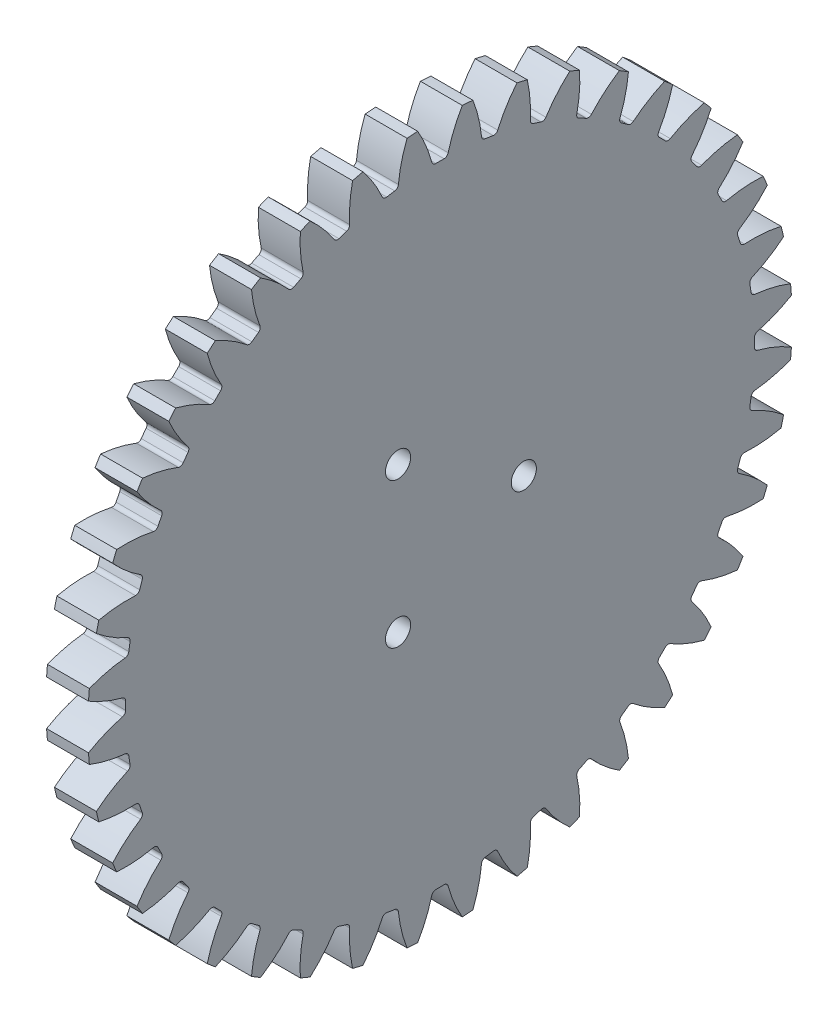
SolidWorks part; units mm, degrees
material "Delrin 2700 NC010, Low Viscosity Acetal Copolymer (SS)"
ref_plane "Plane1" through (0, 0, 0) normal (0, 0, 1) x (1, 0, 0)
ref_plane "Plane2" through (0, 0, 0) normal (0, 1, 0) x (1, 0, 0)
ref_plane "Plane3" through (0, 0, 0) normal (1, 0, 0) x (0, 0, -1)
sketch "HoldingSke" plane through (0, 0, 0) normal (0, 1, 0) x (1, 0, 0)
  line L0 (0, 0) -> (0.383, -0.3214)
  line L1 (-15, 0) -> (100, 0) construction
  line L2 (0, 0) -> (-2.1039, 2.3779)
  line L3 (0, 0) -> (-11.863, 4.5341)
  line L4 (0, 0) -> (6.6156, 5.5511)
  line L5 (0, 0) -> (-46.8476, -17.4728)
  line L6 (0, 0) -> (-4.1448, -2.7965)
  line L7 (-2.1039, 2.3779) -> (8.6586, 51.2059)
  line L8 (-76.2, 54.61) -> (-76.1, 54.61)
  line L9 (-71.009, 38.7566) -> (-53.1078, 45.2721)
  line L10 (-76.2, 71.12) -> (104.1128, 71.12)
  line L11 (0, 0) -> (-5, 0)
  line L12 (-76.2, 101.6) -> (-76.133, 101.6)
  line L13 (24.9733, 27.94) -> (52.9518, 28.4284)
  line L14 (24.9733, 27.94) -> (24.9743, 27.94)
  line L15 (24.9733, 27.94) -> (100.4006, 29.5858)
  line L16 (-63.627, -2) -> (-12.827, -2)
  circle A0 centre (0, 0) radius 0.4
  circle A1 centre (0, 0) radius 37.499
  circle A2 centre (0, 0) radius 37.5
  circle A3 centre (0, 0) radius 0.4
  dimension "MHD" = 74.998
  dimension "Hub_dia" = 75
  dimension "Bore" = 0.8
  dimension "MBD" = 0.8
  dimension "Num_teeth" = 40
  dimension "Pitch" = 0.5
  dimension "Overall_len" = 50
  dimension "Show_teeth" = 40
  dimension "Thickness" = 5
  dimension "OAL" = 50.0001
  dimension "T_dim" = 0.1
  dimension "Ap" = 20
  dimension "H" = 19.05
  dimension "Pitch_radius" = 180.3128
  dimension "Width" = 5
  dimension "Backlash" = 0.067
  dimension "Addendum_fac" = 1
  dimension "Dedendum_fac" = 1.25
  dimension "Clearance_fac" = 0.25
  dimension "Dedendum_add" = 0.001
  dimension "Module" = 2
sketch "BasProSke" plane through (0, 0, 0) normal (0, 1, 0) x (1, 0, 0)
  line L0 (-10, 0) -> (60, 0) construction
  line L1 (0, 0) -> (0, 42)
  line L2 (0, 0) -> (5, 0)
  line L3 (5, 0) -> (5, 42)
  line L4 (5, 42) -> (0, 42)
  dimension "Thickness" = 5
  dimension "Diameter" = 84
revolve "Base-Revolve" add sketch "BasProSke" angle 360 about L0
sketch "TooCutSke" plane through (0, 0, 0) normal (1, 0, 0) x (0, 0, -1)
  line L1 (0, 0) -> (0, 107) construction
  line L2 (0, 0) -> (-1.6876, 39.9644) construction
  line L3 (0, 0) -> (-6.2726, 79.7007) construction
  line L4 (-1.6876, 39.9644) -> (-3.1363, 39.8504) construction
  arc A0 (0.8828, 37.4886) -> (-0.8828, 37.4886) centre (0, 0) ccw
  arc A1 (2.6784, 41.94) -> (-2.6784, 41.94) centre (0, 0) ccw
  circle A2 centre (0, 0) radius 40 construction
  circle A3 centre (0, 0) radius 37.5877 construction
  arc A4 (-0.8828, 37.4886) -> (-2.6784, 41.94) centre (-16.451, 33.7965) ccw
  arc A5 (2.6784, 41.94) -> (0.8828, 37.4886) centre (16.451, 33.7965) ccw
  dimension "Root_dia" = 74.998
  dimension "Overcut_dia" = 84.0508
  dimension "Pitch_dia" = 80
  dimension "Base_dia" = 75.1754
  dimension "Flank_rad" = 16
  dimension "Half_ang" = 4.5
  dimension "Half_CT" = 1.4531
extrude "ToothCut" cut sketch "TooCutSke" along normal through all
fillet "Breaks" [suppressed] radius 0.04 tangent propagation no
fillet "RootFillets" radius 0.501 2 edges at (2.5, 37.4886, -0.8828) (2.5, 37.4886, 0.8828)
pattern_circular "TeethCuts" count 40 every 9 about axis through (-10, 0, 0) along (1, 0, 0) of "ToothCut", "RootFillets", "Breaks"
sketch "HubNeaOneSke" plane through (0, 0, 0) normal (-1, 0, 0) x (0, 0, 1)
  circle A0 centre (0, 0) radius 37.499
  dimension "Diameter" = 74.998
extrude "HubNearOne" [suppressed] add sketch "HubNeaOneSke" along normal blind 45.0001
sketch "HubNeaBotSke" plane through (0, 0, 0) normal (-1, 0, 0) x (0, 0, 1)
  circle A0 centre (0, 0) radius 37.499
  dimension "Diameter" = 74.998
extrude "HubNearBoth" [suppressed] add sketch "HubNeaBotSke" along normal blind 22.5
ref_plane "FarPln" through (5, 0, 0) normal (1, 0, 0) x (0, 0, -1)
sketch "HubFarSke" plane through (5, 0, 0) normal (1, 0, 0) x (0, 0, -1)
  circle A0 centre (0, 0) radius 37.499
  dimension "Diameter" = 74.998
extrude "HubFar" [suppressed] add sketch "HubFarSke" along normal blind 22.5
sketch "BorSke" plane through (0, 0, 0) normal (1, 0, 0) x (0, 0, -1)
  circle A0 centre (0, 0) radius 0.4
  dimension "Diameter" = 0.8
extrude "Bore" [suppressed] cut sketch "BorSke" along normal mid plane 100.0001
sketch "KeySke" plane through (0, 0, 0) normal (1, 0, 0) x (0, 0, -1)
  line L0 (-0.05, 0) -> (-0.05, 0.5)
  line L1 (-0.05, 0.5) -> (0.05, 0.5)
  line L2 (0.05, 0.5) -> (0.05, 0)
  line L3 (0, 0) -> (0, 34) construction
  line L4 (-0.05, 0) -> (0.05, 0)
  dimension "Offset" = 0.5
  dimension "Width" = 0.1
extrude "Keyway" [suppressed] cut sketch "KeySke" along normal mid plane 100.0001
pattern_circular "Keyway2" [suppressed] count 2 every 90 about axis through (-10, 0, 0) along (1, 0, 0) reverse direction yes
sketch "Sketch1" plane through (5, 0, 0) normal (1, 0, 0) x (0, 0, -1)
  line L0 (0, 0) -> (10, 0)
  line L1 (0, 0) -> (-5, 8.6603)
  line L2 (0, 0) -> (-5, -8.6603)
  circle A0 centre (-5, -8.6603) radius 1.5
  circle A1 centre (-5, 8.6603) radius 1.5
  circle A2 centre (10, 0) radius 1.5
  dimension "D6" = 3
  dimension "D7" = 3
  dimension "D8" = 3
  dimension "D1" = 10
  dimension "D2" = 10
  dimension "D3" = 10
  dimension "D4" = 120
  dimension "D5" = 120
extrude "Cut-Extrude1" cut sketch "Sketch1" against normal through all contours A2 | A0 | A1
equation "' \"Module@HoldingSke\" = 6.35"
equation "' \"Num_teeth@HoldingSke\" = 12"
equation "' \"Ap@HoldingSke\" =  20"
equation "' \"Ap@HoldingSke\" = 20"
equation "' \"Width@HoldingSke\" = 0.5 * 25.4"
equation "' \"Hub_dia@HoldingSke\"= 1 * 25.4"
equation "' \"Hub_dia@HoldingSke\" = 1 * 25.4"
equation "' \"Overall_len@HoldingSke\" = 1.0 * 25.4"
equation "' \"Bore@HoldingSke\" = 0.75 * 25.4"
equation "' \"T_dim@HoldingSke\" = 0.1 * 25.4"
equation "' \"Width@KeySke\" = 0.25 * 25.4"
equation "' \"Show_teeth@HoldingSke\" = 13"
equation "' \"Backlash@HoldingSke\" = 0.009 * 25.4"
equation "' \"Addendum_fac@HoldingSke\" = 1.0"
equation "' \"Dedendum_fac@HoldingSke\" = 1.25"
equation "' \"Dedendum_add@HoldingSke\" = 0.00005 * 25.4"
equation "' \"Clearance_fac@HoldingSke\" = 0.25"
equation "\"Pitch@HoldingSke\" = 1 / \"Module@HoldingSke\""
equation "\"Overcut_dia@TooCutSke\" = (\"Num_teeth@HoldingSke\" + 2 * \"Addendum_fac@HoldingSke\") / \"Pitch@HoldingSke\" + 0.002 * 25.4"
equation "\"Pitch_dia@TooCutSke\" = \"Num_teeth@HoldingSke\" / \"Pitch@HoldingSke\""
equation "\"Base_dia@TooCutSke\" = \"Num_teeth@HoldingSke\" / \"Pitch@HoldingSke\" * cos((\"Ap@HoldingSke\"  * 3.14159265 / 180))"
equation "\"Root_dia@TooCutSke\" = (\"Num_teeth@HoldingSke\" + 2) / \"Pitch@HoldingSke\" - 2 * (\"Addendum_fac@HoldingSke\" + \"Dedendum_fac@HoldingSke\") / \"Pitch@HoldingSke\" - \"Dedendum_add@HoldingSke\" * 2"
equation "\"Half_ang@TooCutSke\" = 180 / \"Num_teeth@HoldingSke\""
equation "\"Half_CT@TooCutSke\" = \"Num_teeth@HoldingSke\" / \"Pitch@HoldingSke\" * sin((3.14159265 / 2 / \"Num_teeth@HoldingSke\")) / 2 - 7 * \"Backlash@HoldingSke\" / 4"
equation "\"Flank_rad@TooCutSke\" = \"Num_teeth@HoldingSke\" / \"Pitch@HoldingSke\" / 5"
equation "\"Radius@RootFillets\" = \"Clearance_fac@HoldingSke\" / \"Pitch@HoldingSke\" + \"Dedendum_add@HoldingSke\""
equation "\"Break_rad@Breaks\" = 0.02 / \"Pitch@HoldingSke\""
equation "\"Thickness@HoldingSke\" = \"Width@HoldingSke\""
equation "\"OAL@HoldingSke\" = \"Thickness@HoldingSke\""
equation "\"MHD@HoldingSke\" = (\"Num_teeth@HoldingSke\" + 2) / \"Pitch@HoldingSke\" - 2 * (\"Addendum_fac@HoldingSke\" + \"Dedendum_fac@HoldingSke\")  / \"Pitch@HoldingSke\" - \"Dedendum_add@HoldingSke\" * 2"
equation "\"MBD@HoldingSke\" = (\"Num_teeth@HoldingSke\" + 2) / \"Pitch@HoldingSke\" - 2 * (\"Addendum_fac@HoldingSke\" + \"Dedendum_fac@HoldingSke\")  / \"Pitch@HoldingSke\" - \"Dedendum_add@HoldingSke\" * 2 - 0.002 * 25.4"
equation "\"MHD@HoldingSke\" = ((sgn( \"MHD@HoldingSke\" - \"Hub_dia@HoldingSke\" )-1)*( \"MHD@HoldingSke\" - \"Hub_dia@HoldingSke\" ))/-2+ \"Hub_dia@HoldingSke\""
equation "\"MBD@HoldingSke\" = ((sgn( \"MBD@HoldingSke\" - \"Bore@HoldingSke\" )-1)*( \"MBD@HoldingSke\" - \"Bore@HoldingSke\" ))/-2+ \"Bore@HoldingSke\""
equation "\"OAL@HoldingSke\" = ((sgn( \"OAL@HoldingSke\" - \"Overall_len@HoldingSke\" )+1)*( \"OAL@HoldingSke\" - \"Overall_len@HoldingSke\" ))/2 + \"Overall_len@HoldingSke\" + 0.000002 * 25.4"
equation "\"Num_teeth@TeethCuts\" = int( \"Show_teeth@HoldingSke\" ) + 1"
equation "\"Num_teeth@TeethCuts\" = ((sgn( \"Num_teeth@TeethCuts\" - \"Num_teeth@HoldingSke\" )-1)*( \"Num_teeth@TeethCuts\" - \"Num_teeth@HoldingSke\" ))/-2+ \"Num_teeth@HoldingSke\""
equation "\"Num_teeth@TeethCuts\" = ((sgn( \"Num_teeth@TeethCuts\" - 2.0)+1)*( \"Num_teeth@TeethCuts\" - 2.0))/2 +2.0"
equation "\"Angle@TeethCuts\" = 360.0 / \"Num_teeth@HoldingSke\""
equation "\"Diameter@BasProSke\" = (\"Num_teeth@HoldingSke\" + 2 * \"Addendum_fac@HoldingSke\") / \"Pitch@HoldingSke\""
equation "\"Thickness@BasProSke\"  = \"Thickness@HoldingSke\""
equation "' \"Fillet_rad@BasProSke\" =  \"Thickness@HoldingSke\" * 0.05"
equation "' \"Fillet_rad@BasProSke\" = \"Thickness@HoldingSke\" * 0.05"
equation "\"MHD@HoldingSke\" = ((sgn( \"MHD@HoldingSke\" - \"Root_dia@TooCutSke\" )-1)*( \"MHD@HoldingSke\" - \"Root_dia@TooCutSke\" ))/-2+ \"Root_dia@TooCutSke\""
equation "\"Diameter@HubNeaOneSke\" = \"MHD@HoldingSke\""
equation "\"Length@HubNearOne\" = \"OAL@HoldingSke\" - \"Thickness@BasProSke\""
equation "\"Diameter@HubNeaBotSke\" = \"MHD@HoldingSke\""
equation "\"Length@HubNearBoth\" = ( \"OAL@HoldingSke\" - \"Thickness@BasProSke\" ) / 2.0"
equation "\"Thickness@FarPln\" = \"Thickness@BasProSke\""
equation "\"Diameter@HubFarSke\" = \"MHD@HoldingSke\""
equation "\"Length@HubFar\" = ( \"OAL@HoldingSke\" - \"Thickness@BasProSke\" ) / 2.0"
equation "\"Diameter@BorSke\" = \"MBD@HoldingSke\""
equation "\"D1@Bore\" = \"OAL@HoldingSke\" * 2.0"
equation "\"D1@Keyway\" = \"OAL@HoldingSke\" * 2.0"
equation "\"Offset@KeySke\" = \"T_dim@HoldingSke\" + \"MBD@HoldingSke\" / 2.0"
